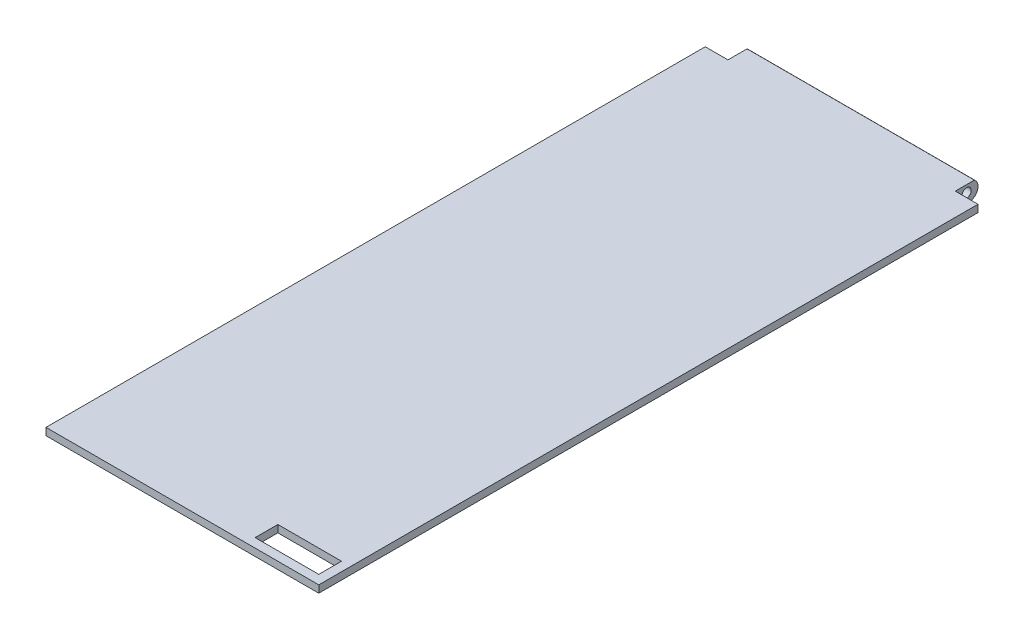
SolidWorks part; units mm, degrees
ref_plane "Front Plane" through (0, 0, 0) normal (0, 0, 1) x (1, 0, 0)
ref_plane "Top Plane" through (0, 0, 0) normal (0, 1, 0) x (1, 0, 0)
ref_plane "Right Plane" through (0, 0, 0) normal (1, 0, 0) x (0, 0, -1)
sketch "Sketch1" plane through (0, 0, 0) normal (0, 1, 0) x (1, 0, 0)
  line L1 (-15, -35) -> (15, -35)
  line L2 (-15, -35) -> (-15, 35)
  line L3 (-15, 35) -> (15, 35)
  line L4 (15, -35) -> (15, 35)
  line L5 (-15, -35) -> (15, 35) construction
  line L6 (-15, 35) -> (15, -35) construction
  point P0 (0, 0)
  dimension "D1" = 70
  dimension "D2" = 30
extrude "Boss-Extrude1" add sketch "Sketch1" along normal blind 1 contours L2 L3 L4 L1
sketch "Sketch2" plane through (0, 0, 0) normal (0, 1, 0) x (1, 0, 0)
  line L0 (15, -35) -> (15, 35) construction
  line L1 (-15, 35) -> (15, 35)
  line L2 (-15, 35) -> (-15, 32.5)
  line L3 (-15, 32.5) -> (15, 32.5)
  line L4 (15, 35) -> (15, 32.5)
  dimension "D1" = 2.5
sketch "Sketch5" plane through (0, 0, 35) normal (0, 0, 1) x (1, 0, 0)
  line L1 (-15, 1) -> (15, 1)
  line L2 (-15, 1) -> (-15, 0)
  line L3 (-15, 0) -> (15, 0)
  line L4 (15, 1) -> (15, 0)
extrude "Boss-Extrude3" add sketch "Sketch5" along normal blind 5
sketch "Sketch6" plane through (0, 1, 0) normal (0, 1, 0) x (1, 0, 0)
  line L0 (15, -40) -> (15, 35) construction
  line L1 (7, -36.5) -> (14, -36.5)
  line L2 (7, -36.5) -> (7, -39)
  line L3 (7, -39) -> (14, -39)
  line L4 (14, -36.5) -> (14, -39)
  line L5 (15, -40) -> (-15, -40) construction
  dimension "D1" = 2.5
  dimension "D2" = 7
  dimension "D3" = 1
  dimension "D4" = 1
extrude "Cut-Extrude3" cut sketch "Sketch6" against normal up to vertex (1 mm away) up to point (15, 0, 40)
extrude "Boss-Extrude4" add sketch "Sketch2" against normal blind 1 contours L1 L4 L3 L2
sketch "Sketch7" plane through (-15, 0, 0) normal (-1, 0, 0) x (0, 0, 1)
  line L0 (-32.5, -1) -> (-32.5, 0) construction
  line L1 (-35, -1) -> (-32.5, -1) construction
  circle A0 centre (-33.75, 0) radius 0.5
  dimension "D3" = 1
  dimension "D1" = 1.25
  dimension "D2" = 1
extrude "Cut-Extrude4" cut sketch "Sketch7" against normal up to vertex (30 mm away) up to point (15, 1, -35)
fillet "Fillet1" radius 1 2 edges at (0, -1, -35) (0, 1, -35)
sketch "Sketch9" plane through (-15, 0, 0) normal (-1, 0, 0) x (0, 0, 1)
  line L1 (-32.5, -1) -> (-35.5, -1)
  line L2 (-32.5, -1) -> (-32.5, 1)
  line L3 (-32.5, 1) -> (-35.5, 1)
  line L4 (-35.5, -1) -> (-35.5, 1)
  dimension "D1" = 2
  dimension "D2" = 3
extrude "Cut-Extrude5" cut sketch "Sketch9" against normal blind 2.5
sketch "Sketch10" plane through (15, 0, 0) normal (1, 0, 0) x (0, 0, -1)
  line L1 (32.5, -1) -> (35.5, -1)
  line L2 (32.5, -1) -> (32.5, 1)
  line L3 (32.5, 1) -> (35.5, 1)
  line L4 (35.5, -1) -> (35.5, 1)
  dimension "D1" = 2
  dimension "D2" = 3
extrude "Cut-Extrude6" cut sketch "Sketch10" against normal blind 2.5
sketch "Sketch11" plane through (0, 1, 0) normal (0, 1, 0) x (1, 0, 0)
  line L1 (15, -40) -> (-18.9676, -40)
  line L2 (15, -40) -> (15, 36.4266)
  line L3 (15, 36.4266) -> (-18.9676, 36.4266)
  line L4 (-18.9676, -40) -> (-18.9676, 36.4266)
  point P5 (-18.9676, 34.4729)
  point P6 (15, 33.8868)
  point P7 (0, 0)
  point P8 (15, 36.4266)
extrude "Cut-Extrude7" cut sketch "Sketch11" against normal blind 0.2
